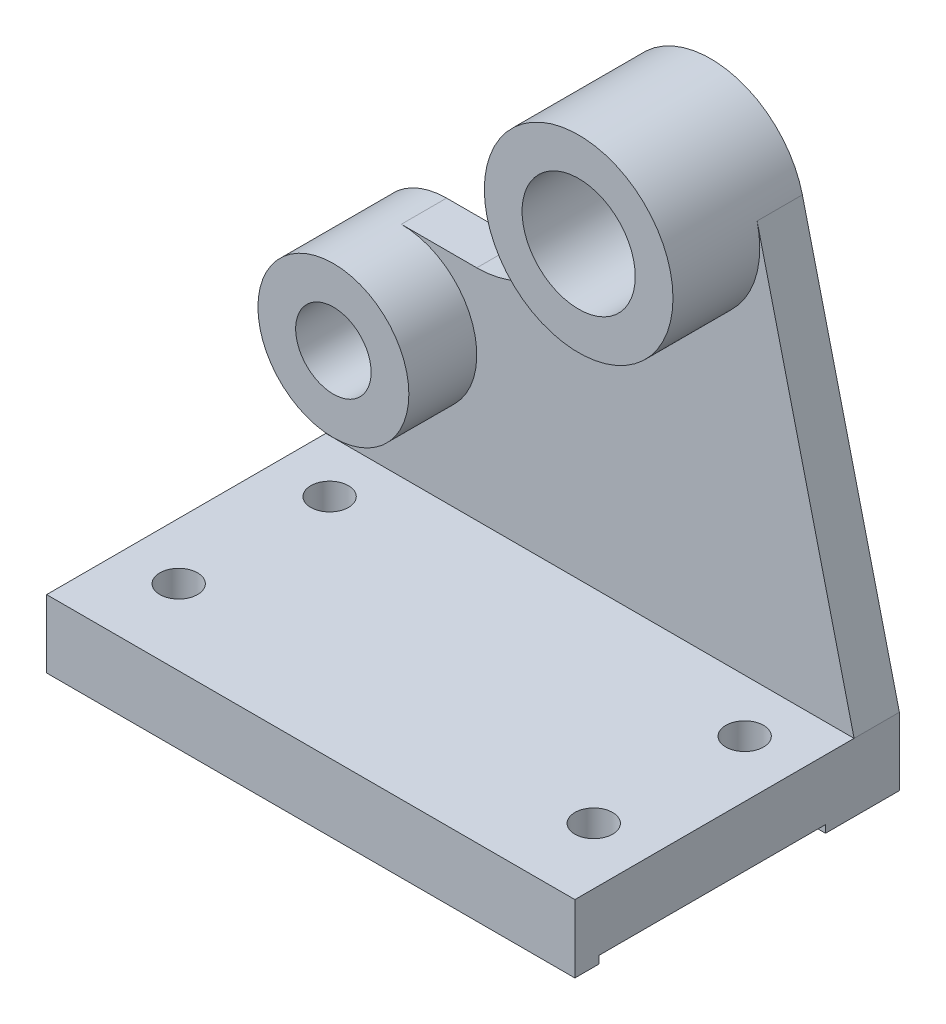
SolidWorks part; units mm, degrees
ref_plane "Front Plane" through (0, 0, 0) normal (0, 0, 1) x (1, 0, 0)
ref_plane "Top Plane" through (0, 0, 0) normal (0, 1, 0) x (1, 0, 0)
ref_plane "Right Plane" through (0, 0, 0) normal (1, 0, 0) x (0, 0, -1)
sketch "Sketch4" plane through (0, 0, 0) normal (0, 0, 1) x (1, 0, 0)
  line L1 (-70, 0) -> (70, 0)
  line L2 (-70, 0) -> (-70, -18)
  line L3 (-70, -18) -> (70, -18)
  line L4 (70, 0) -> (70, -18)
  dimension "D1" = 18
  dimension "D2" = 140
sketch "Sketch5" plane through (0, 0, 0) normal (0, 0, 1) x (1, 0, 0)
extrude "Boss-Extrude1" add sketch "Sketch4" along normal blind 86
sketch "Sketch6" plane through (0, 0, 0) normal (0, 0, 1) x (1, 0, 0)
  line L1 (70, -18) -> (70, 0) construction
  line L2 (-70, -18) -> (70, -18) construction
  line L3 (-70, 0) -> (70, 0)
  line L4 (70, 0) -> (44.2945, 105.8972)
  line L5 (-70, 0) -> (-70, 38)
  line L6 (-50, 58) -> (-30, 58)
  line L7 (-5, 100) -> (-5, 83)
  circle A0 centre (20, 100) radius 25
  circle A1 centre (20, 100) radius 15
  circle A2 centre (-50, 38) radius 20
  circle A3 centre (-50, 38) radius 10
  arc A4 (-30, 58) -> (-5, 83) centre (-30, 83) ccw
  dimension "D1" = 40
  dimension "D2" = 50
  dimension "D3" = 30
  dimension "D5" = 50
  dimension "D6" = 20
  dimension "D7" = 56
  dimension "D8" = 25
  dimension "D4" = 118
extrude "Boss-Extrude3" add sketch "Sketch6" along normal blind 12 contours A4 L6 A2 L5 L3 L4 A0 L7 region at (9.4951, 34.5701, 0)
extrude "Boss-Extrude4" add sketch "Sketch6<5>" along normal blind 35 contours A0 A1 region at (44.1209, 102.8857, 0)
sketch "Sketch6<5>" plane through (0, 0, 0) normal (0, 0, 1) x (1, 0, 0) same geometry as "Sketch6"
extrude "Boss-Extrude5" add sketch "Sketch6<6>" along normal blind 30 contours A2 A3 region at (-63.7421, 51.7421, 0)
sketch "Sketch6<6>" plane through (0, 0, 0) normal (0, 0, 1) x (1, 0, 0) same geometry as "Sketch6"
sketch "Sketch11" plane through (0, 0, 0) normal (0, 1, 0) x (1, 0, 0)
  line L0 (-70, -86) -> (-70, -12) construction
  line L1 (-55, -26) -> (55, -26) construction
  line L2 (-55, -26) -> (-55, -66) construction
  line L3 (-55, -66) -> (55, -66) construction
  line L4 (55, -26) -> (55, -66) construction
  line L5 (70, -86) -> (-70, -86) construction
  circle A0 centre (-55, -66) radius 5
  circle A1 centre (-55, -26) radius 5
  circle A2 centre (55, -26) radius 5
  circle A3 centre (55, -66) radius 5
  dimension "D5" = 10
  dimension "D1" = 110
  dimension "D2" = 40
  dimension "D3" = 15
  dimension "D4" = 20
extrude "Cut-Extrude1" cut sketch "Sketch11" against normal through all
sketch "Sketch12" plane through (70, 0, 0) normal (1, 0, 0) x (0, 0, -1)
  line L0 (-86, -18) -> (0, -18) construction
  line L1 (-79.5757, -16) -> (-19.5757, -16)
  line L2 (-79.5757, -16) -> (-79.5757, -32.1797)
  line L3 (-79.5757, -32.1797) -> (-19.5757, -32.1797)
  line L4 (-19.5757, -16) -> (-19.5757, -32.1797)
  line L5 (0, 91.6373) -> (0, -91.6373) construction
  dimension "D1" = 60
  dimension "D2" = 2
  dimension "D3" = 19.5757
extrude "Cut-Extrude2" cut sketch "Sketch12" against normal through all
